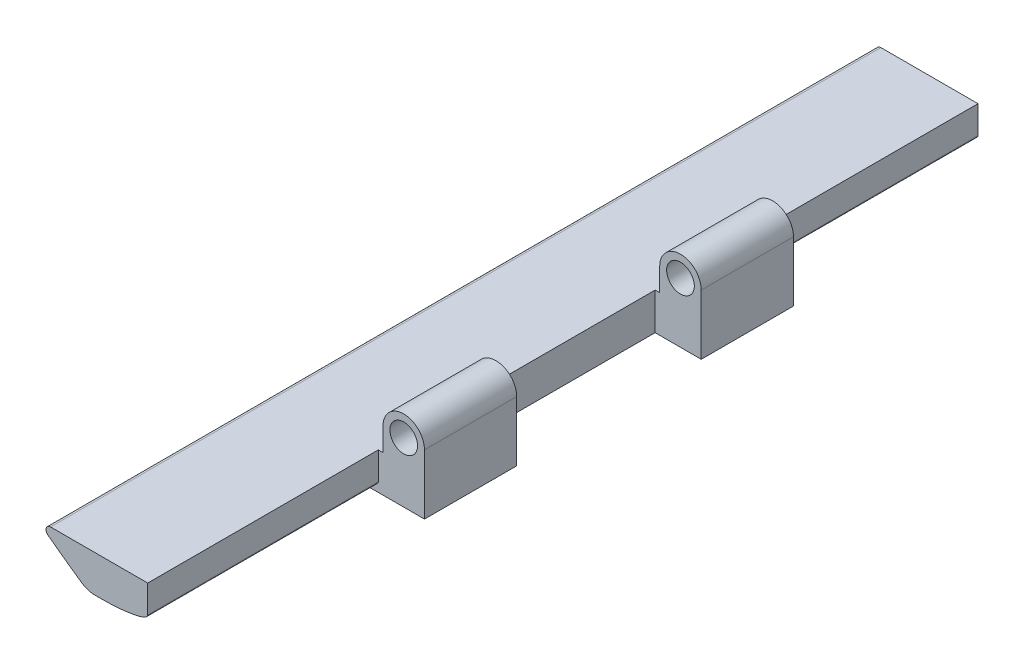
SolidWorks part; units mm, degrees
material "ABS"
ref_plane "Front Plane" through (0, 0, 0) normal (0, 0, 1) x (1, 0, 0)
ref_plane "Top Plane" through (0, 0, 0) normal (0, 1, 0) x (1, 0, 0)
ref_plane "Right Plane" through (0, 0, 0) normal (1, 0, 0) x (0, 0, -1)
sketch "Sketch1" plane through (0, 0, 0) normal (0, 0, 1) x (1, 0, 0)
  line L0 (41.1966, -4.0634) -> (66.1966, -4.0634)
  line L1 (66.1966, -4.0634) -> (66.1966, -12.0634)
  line L2 (66.1966, -12.0634) -> (52.1966, -12.0634)
  line L3 (66.1966, -4.0634) -> (66.1966, 0.9366)
  line L4 (66.1966, -12.0634) -> (75.1966, -12.0634)
  line L5 (75.1966, -12.0634) -> (75.1966, 0.9366)
  arc A0 (41.1966, -4.0634) -> (52.1966, -12.0634) centre (171.3374, 163.3176) ccw
  arc A1 (75.1966, 0.9366) -> (66.1966, 0.9366) centre (70.6966, 0.9366) ccw
  circle A2 centre (70.6966, 0.9366) radius 3
  point P10 (41.1966, -4.0634)
  point P11 (-100.981, 18.4407)
  dimension "D6" = 6
  dimension "D1" = 8
  dimension "D2" = 25
  dimension "D3" = 14
  dimension "D4" = 13
  dimension "D5" = 9
extrude "Boss-Extrude2" add sketch "Sketch1" along normal blind 180 contours L5 A1 L3 L1 L4 A2 | L0 A0 L2 L1 region at (56.1281, -7.69, 0) region at (70.6966, -4.8688, 0)
sketch "Sketch3" plane through (0, -12.0634, 0) normal (0, -1, 0) x (1, 0, 0)
  line L1 (75.1966, 180) -> (65.1966, 180)
  line L2 (75.1966, 180) -> (75.1966, 130)
  line L3 (75.1966, 130) -> (65.1966, 130)
  line L4 (65.1966, 180) -> (65.1966, 130)
  line L5 (75.1966, 0) -> (65.1966, 0)
  line L6 (75.1966, 0) -> (75.1966, 50)
  line L7 (75.1966, 50) -> (65.1966, 50)
  line L8 (65.1966, 0) -> (65.1966, 50)
  dimension "D1" = 50
  dimension "D2" = 50
  dimension "D3" = 10
  dimension "D4" = 10
extrude "Cut-Extrude1" cut sketch "Sketch3" against normal blind 32
sketch "Sketch4" plane through (0, -12.0634, 0) normal (0, -1, 0) x (-1, 0, 0)
  line L0 (-75.1966, -130) -> (-75.1966, -50) construction
  line L1 (-75.1966, -110) -> (-65.1966, -110)
  line L2 (-75.1966, -110) -> (-75.1966, -70)
  line L3 (-75.1966, -70) -> (-65.1966, -70)
  line L4 (-65.1966, -110) -> (-65.1966, -70)
  line L5 (-65.1966, -130) -> (-75.1966, -130) construction
  dimension "D1" = 40
  dimension "D2" = 20
  dimension "D3" = 10
extrude "Cut-Extrude2" cut sketch "Sketch4" against normal blind 32
fillet "Fillet3" radius 1 1 edges at (41.1966, -4.0634, 90)
fillet "Fillet4" radius 5 1 edges at (52.1966, -12.0634, 90)
fillet "Fillet5" radius 10 2 edges at (65.1966, -12.0634, 25) (65.1966, -12.0634, 155) second distance 2 first distance on face at (66.6213, -12.0634, 90)
